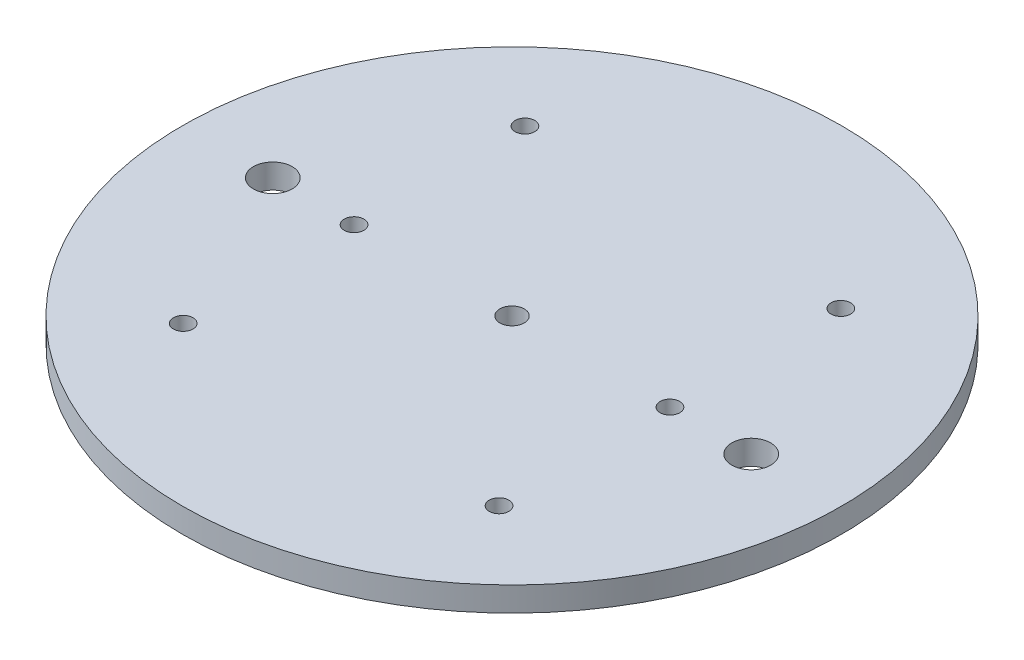
SolidWorks part; units mm, degrees
material "Malleable Cast Iron"
ref_plane "Front Plane" through (0, 0, 0) normal (0, 0, 1) x (1, 0, 0)
ref_plane "Top Plane" through (0, 0, 0) normal (0, 1, 0) x (1, 0, 0)
ref_plane "Right Plane" through (0, 0, 0) normal (1, 0, 0) x (0, 0, -1)
sketch "Sketch12" plane through (0, 0, 0) normal (0, 1, 0) x (1, 0, 0)
  line B0 (-31.369, -69.0517) -> (-31.369, 69.0517) construction
  line B1 (50.8, -69.0517) -> (50.8, 69.0517) construction
  line B2 (50.8, -69.0517) -> (-50.8, -69.0517) construction
  line B3 (-50.8, -69.0517) -> (-50.8, 69.0517) construction
  line B4 (50.8, 69.0517) -> (-50.8, 69.0517) construction
  line B5 (31.369, 69.0517) -> (31.369, -69.0517) construction
  circle B6 centre (0, 0) radius 85.725
  line B7 (-31.369, 0) -> (31.369, 0) construction
  line B8 (41.0845, -69.0517) -> (41.0845, 69.0517) construction
  line B9 (31.369, 0) -> (50.8, 0) construction
  line B10 (-31.369, 0) -> (-50.8, 0) construction
  line B11 (-41.0845, 44.45) -> (41.0845, -44.45) construction
  line B12 (-41.0845, -69.0517) -> (-41.0845, 69.0517) construction
  line B13 (-41.0845, -44.45) -> (41.0845, 44.45) construction
  line B14 (-50.8, 0) -> (-85.725, 0) construction
  line B15 (50.8, 0) -> (85.725, 0) construction
  line B16 (0, -85.725) -> (0, 85.725) construction
sketch_block_instance "swivel plate-3"
sketch_block "swivel plate" parameters "D1"=171.45, "D2"=32.9884, "D3"=88.1371, "D4"=89.3617, "D5"=152.4754
sketch "Sketch1" plane through (0, 0, 0) normal (0, 1, 0) x (1, 0, 0)
  circle A0 centre (0, 0) radius 85.725 construction
  circle A1 centre (0, 0) radius 85.725
extrude "Boss-Extrude1" add sketch "Sketch1" along normal blind 6.35
hole_wizard "3/8 Clearance Hole1" positions "Sketch6" profile "Sketch7" hole size "3/8" standard "ANSI Inch" end condition through all
sketch "Sketch6" plane through (0, 6.35, 0) normal (0, 1, 0) x (0.9997, 0, 0.0242)
  point P14 (-62.2117, -1.5089)
  point P16 (62.2117, 1.5089)
  point P18 (62.2117, 1.5089)
  point P19 (-62.2117, -1.5089)
sketch "Sketch7" plane through (-62.23, 6.35, 0) normal (1, 0, 0) x (0, 0, 1)
  line L0 (0, 0) -> (0, 6.35)
  line L1 (0, 6.35) -> (5.0419, 6.35)
  line L2 (5.0419, 6.35) -> (5.0419, 0)
  line L5 (5.0419, 0) -> (0, 0)
  line L11 (0, -6.35) -> (0, 107.95) construction
  dimension "Thru Hole Dia." = 10.0838
  dimension "Thru Hole Depth" = 6.35
hole_wizard "1/4 (0.25) Clearance Dowel Hole1" positions "Sketch8" profile "Sketch9" hole size "1/4" standard "ANSI Inch" end condition through all
sketch "Sketch8" plane through (43.3774, 6.35, -259.2845) normal (0, 1, 0) x (0.9888, 0, -0.1489)
  point P3 (-81.5106, -249.9322)
sketch "Sketch9" plane through (0, 6.35, 0) normal (1, 0, 0) x (0, 0, 1)
  line L0 (0, 0) -> (0, 6.35)
  line L1 (0, 6.35) -> (3.175, 6.35)
  line L2 (3.175, 6.35) -> (3.175, 0)
  line L3 (3.175, 0) -> (0, 0)
  line L4 (0, -6.35) -> (0, 107.95) construction
  dimension "Thru Hole Dia." = 6.35
  dimension "Thru Hole Depth" = 6.35
hole_wizard "#10 Clearance Hole1" positions "Sketch10" profile "Sketch11" hole size "#10" standard "ANSI Inch" end condition up to next
sketch "Sketch10" plane through (43.3774, 0, -259.2845) normal (0, -1, 0) x (-0.9888, 0, 0.1489)
  point P22 (115.5166, -199.859)
  point P24 (122.1369, -243.8132)
  point P26 (128.7571, -287.7674)
  point P28 (34.2641, -212.0969)
  point P30 (40.8843, -256.0512)
  point P32 (47.5046, -300.0054)
sketch "Sketch11" plane through (-41.0845, 0, -44.45) normal (1, 0, 0) x (0, 0, -1)
  line L0 (0, 0) -> (0, 6.35)
  line L1 (0, 6.35) -> (2.5527, 6.35)
  line L2 (2.5527, 6.35) -> (2.5527, 0)
  line L5 (2.5527, 0) -> (0, 0)
  line L11 (0, -6.35) -> (0, 107.95) construction
  dimension "Thru Hole Dia." = 5.1054
  dimension "Thru Hole Depth" = 6.35
equation "\"delta-z\" = 1.5"
equation "\"total-height\" = 3.28"
equation "\"mid-height\" = 1.5"
equation "\"jaw-width\" = 4"
equation "\"jaw-height\" = \"total-height\" - \"mid-height\""
equation "\"max-tube-diam\" = 3.5"
equation "\"v-block-notch-height\" = 1.5"
equation "\"v-block-notch-angle\" = 120"
equation "\"jaw-travel\" = 4.45"
equation "\"rib-top-width\" = 0.5"
equation "\"rib-side-width\" = 0.5"
equation "\"quarter-twenty-close-clearance\" = .257"
equation "\"box-way-width\" = 1.5"
equation "\"box-way-depth\" = 1.5"
equation "\"screw-OD\" = .625"
equation "\"screw-reduced-diam\" = .47"
equation "\"pressure-plate-OD\" = 6.75"
equation "\"D1@swivel plate\"=\"pressure-plate-OD\""
equation "\"D2@swivel plate\"=\"jaw-width\""
equation "\"D3@swivel plate\"=2.47"
